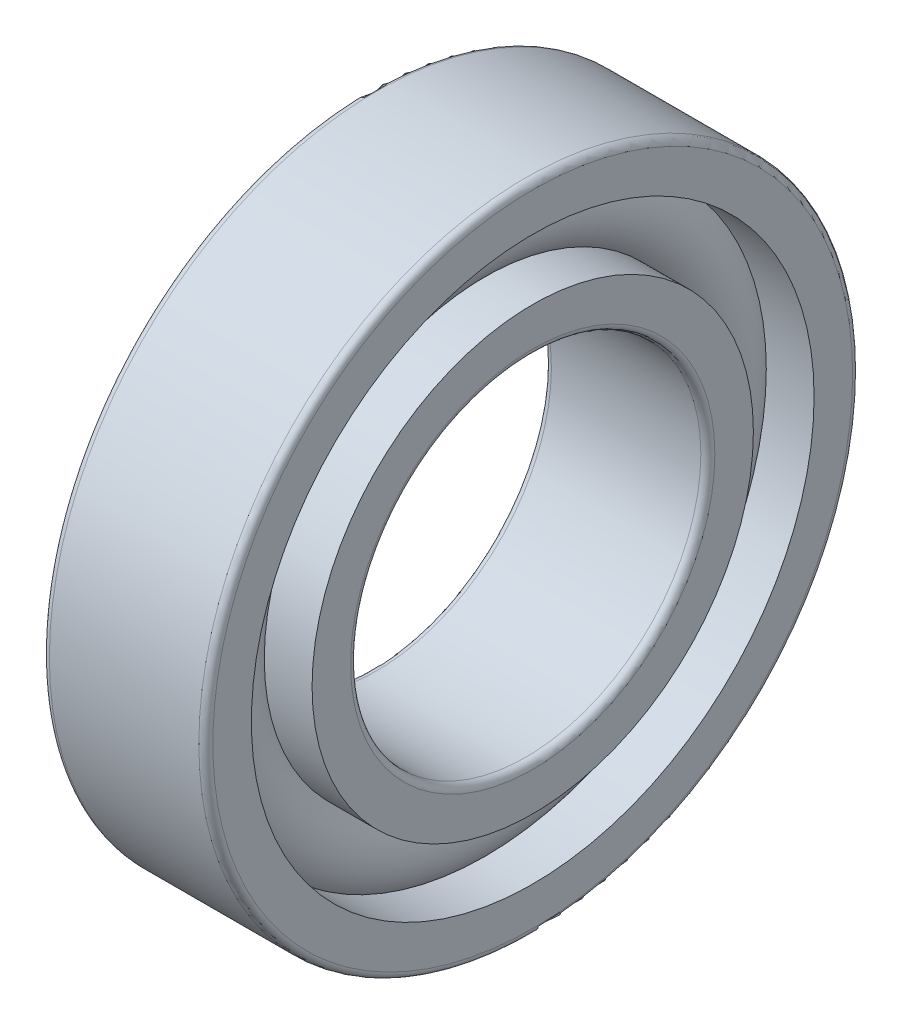
SolidWorks part; units mm, degrees
ref_plane "Plane1" through (0, 0, 0) normal (0, 0, 1) x (1, 0, 0)
ref_plane "Plane2" through (0, 0, 0) normal (0, 1, 0) x (1, 0, 0)
ref_plane "Plane3" through (0, 0, 0) normal (1, 0, 0) x (0, 0, -1)
sketch "Clipboard" plane through (0, 0, 0) normal (0, 0, 1) x (1, 0, 0)
  line L0 (-10, 0) -> (10, 0) construction
  line L1 (0, 0) -> (22.3471, -0.7804)
  line L2 (0, 0) -> (10.7435, 0.3752)
  line L3 (0, 0) -> (22.3471, -0.7804)
  line L4 (0, 0) -> (-22.3573, -0.3902)
  dimension "BallCLRad" = 10.75
sketch "CagSpiSke" plane through (0, 0, 0) normal (0, 0, 1) x (1, 0, 0)
  line L0 (0.195, 10.425) -> (0.195, 11.075)
  line L1 (0.195, 11.075) -> (-0.195, 11.075)
  line L2 (-0.195, 11.075) -> (-0.195, 10.425)
  line L3 (-0.195, 10.425) -> (0.195, 10.425)
  line L4 (-20.6375, 0) -> (20.6375, 0) construction
  line L5 (0, 0) -> (0, 23.7692) construction
  dimension "OD" = 22.15
  dimension "ID" = 20.85
revolve "CageSpine" add sketch "CagSpiSke" angle 0.001 about L4 reverse direction yes
ref_axis "Axis1" through (-50, 0, 0) along (1, 0, 0)
sketch "CagBalSke" plane through (0, 0, 0) normal (0, 0, 1) x (1, 0, 0)
  line L0 (-2.145, 10.75) -> (2.145, 10.75)
  line L1 (-1.905, 10.75) -> (1.905, 10.75) construction
  line L2 (-10, 0) -> (10, 0) construction
  line L3 (0, 0) -> (0, 24) construction
  arc A0 (2.145, 10.75) -> (-2.145, 10.75) centre (0, 10.75) cw
  dimension "BallCLRad" = 10.75
revolve "CageBall" [suppressed] add sketch "CagBalSke" angle 360 about L1 reverse direction yes
pattern_circular "CageBalls" [suppressed] count 2 every 180 about axis through (-50, 0, 0) along (1, 0, 0)
sketch "CagTrmODSke" plane through (0, 0, 0) normal (0, 0, 1) x (1, 0, 0)
  line L0 (2.146, 11.075) -> (2.146, 12.896)
  line L1 (2.146, 12.896) -> (-2.146, 12.896)
  line L2 (-2.146, 12.896) -> (-2.146, 11.075)
  line L3 (-2.146, 11.075) -> (2.146, 11.075)
  line L4 (-20.6375, 0) -> (20.6375, 0) construction
  line L5 (0, 0) -> (0, 25) construction
  dimension "Width" = 4.292
  dimension "ID" = 22.15
  dimension "OD" = 25.792
revolve "CageTrimOD" [suppressed] cut sketch "CagTrmODSke" angle 360 about L4 reverse direction yes
sketch "CagTrmIDSke" plane through (0, 0, 0) normal (0, 0, 1) x (1, 0, 0)
  line L0 (2.146, 8.606) -> (2.146, 10.425)
  line L1 (2.146, 10.425) -> (-2.146, 10.425)
  line L2 (-2.146, 10.425) -> (-2.146, 8.606)
  line L3 (-2.146, 8.606) -> (2.146, 8.606)
  line L4 (-20.6375, 0) -> (20.6375, 0) construction
  line L5 (0, 0) -> (0, 25) construction
  dimension "Width" = 4.292
  dimension "ID" = 17.212
  dimension "OD" = 20.85
revolve "CageTrimID" [suppressed] cut sketch "CagTrmIDSke" angle 360 about L4 reverse direction yes
sketch "BalSimSke" plane through (0, 0, 0) normal (0, 0, 1) x (1, 0, 0)
  line L0 (-10, 0) -> (10, 0) construction
  line L1 (-10, 10.75) -> (10, 10.75) construction
  line L2 (0, 0) -> (0, 23) construction
  circle A0 centre (0, 10.75) radius 1.95
  dimension "BallCLRad" = 10.75
  dimension "Ball_diameter" = 3.9
revolve "BallsSimplified" add sketch "BalSimSke" angle 360 about L0
sketch "BalDetSke" plane through (0, 0, 0) normal (0, 0, 1) x (1, 0, 0)
  line L0 (-1.95, 10.75) -> (1.95, 10.75)
  line L1 (-1.905, 10.75) -> (1.905, 10.75) construction
  line L2 (0, 0) -> (0, 25) construction
  arc A0 (1.95, 10.75) -> (-1.95, 10.75) centre (0, 10.75) cw
  dimension "BallCLRad" = 10.75
  dimension "Ball_diameter" = 3.9
revolve "BallDetailed" [suppressed] add sketch "BalDetSke" angle 360 about L1 reverse direction yes
sketch "InnRacSke" plane through (0, 0, 0) normal (0, 0, 1) x (1, 0, 0)
  line L0 (-1.4197, 9.45) -> (-3.5, 9.45)
  line L1 (-3.5, 9.45) -> (-3.5, 7.8)
  line L2 (-3.2, 7.5) -> (3.2, 7.5)
  line L3 (3.5, 7.8) -> (3.5, 9.45)
  line L4 (3.5, 9.45) -> (1.4197, 9.45)
  line L5 (-20.6375, 0) -> (20.6375, 0) construction
  line L6 (0, 0) -> (0, 30) construction
  arc A0 (-3.5, 7.8) -> (-3.2, 7.5) centre (-3.2, 7.8) ccw
  arc A1 (3.2, 7.5) -> (3.5, 7.8) centre (3.2, 7.8) ccw
  arc A2 (1.4197, 9.45) -> (-1.4197, 9.45) centre (0, 10.75) cw
  dimension "BallCLRad" = 10.75
  dimension "Fillet_radius" = 0.3
  dimension "Ball_diameter" = 3.85
  dimension "ID" = 15
  dimension "OD" = 18.9
  dimension "Width" = 7
revolve "InnerRace" add sketch "InnRacSke" angle 360 about L5 reverse direction yes
sketch "OutRacSke" plane through (0, 0, 0) normal (0, 0, 1) x (1, 0, 0)
  line L0 (-1.4197, 12.05) -> (-3.5, 12.05)
  line L1 (-3.5, 12.05) -> (-3.5, 13.7)
  line L2 (-3.2, 14) -> (3.2, 14)
  line L3 (3.5, 13.7) -> (3.5, 12.05)
  line L4 (3.5, 12.05) -> (1.4197, 12.05)
  line L5 (-20.6375, 0) -> (20.6375, 0) construction
  line L6 (0, 0) -> (0, 30) construction
  arc A0 (-3.5, 13.7) -> (-3.2, 14) centre (-3.2, 13.7) cw
  arc A1 (3.2, 14) -> (3.5, 13.7) centre (3.2, 13.7) cw
  arc A2 (1.4197, 12.05) -> (-1.4197, 12.05) centre (0, 10.75) ccw
  dimension "BallCLRad" = 10.75
  dimension "Fillet_radius" = 0.3
  dimension "Ball_diameter" = 3.85
  dimension "Width" = 7
revolve "OuterRace" add sketch "OutRacSke" angle 360 about L5 reverse direction yes
pattern_circular "BallsDetailed" [suppressed] count 2 every 180 about axis through (-50, 0, 0) along (1, 0, 0)
equation "\"BallCLRad@Clipboard\" = ( \"OD@OutRacSke\" + \"ID@InnRacSke\" ) / 4"
equation "\"BallCLRad@BalSimSke\" = \"BallCLRad@Clipboard\""
equation "\"BallCLRad@BalDetSke\" = \"BallCLRad@Clipboard\""
equation "\"BallCLRad@InnRacSke\" = \"BallCLRad@Clipboard\""
equation "\"BallCLRad@OutRacSke\" = \"BallCLRad@Clipboard\""
equation "\"Ball_diameter@InnRacSke\" = \"Ball_diameter@BalDetSke\" - 0.05"
equation "\"Ball_diameter@OutRacSke\" = \"Ball_diameter@BalDetSke\" - 0.05"
equation "\"Ball_diameter@BalSimSke\" = \"Ball_diameter@BalDetSke\""
equation "\"Width@OutRacSke\" = \"Width@InnRacSke\""
equation "\"Fillet_radius@OutRacSke\" = \"Fillet_radius@InnRacSke\""
equation "\"Max_count@Clipboard\" = int( 3.14159265 / atn(( \"Ball_diameter@BalDetSke\" / 2) / sqr( \"BallCLRad@Clipboard\"  *  \"BallCLRad@Clipboard\" - ( \"Ball_diameter@BalDetSke\" / 2) *  ( \"Ball_diameter@BalDetSke\" / 2))))"
equation "\"Max_count@Clipboard\" = ((sgn( \"Max_count@Clipboard\" - \"Count@Clipboard\" )-1)*( \"Max_count@Clipboard\" - \"Count@Clipboard\" ))/-2+ \"Count@Clipboard\""
equation "\"Count@BallsDetailed\" = int( \"Show_count@Clipboard\" ) "
equation "\"Count@BallsDetailed\" = ((sgn( \"Count@BallsDetailed\" - \"Max_count@Clipboard\" )-1)*( \"Count@BallsDetailed\" - \"Max_count@Clipboard\" ))/-2+ \"Max_count@Clipboard\""
equation "\"Count@BallsDetailed\" = ((sgn( \"Count@BallsDetailed\" - \"Min_count@Clipboard\" )+1)*( \"Count@BallsDetailed\" - \"Min_count@Clipboard\"))/2 +\"Min_count@Clipboard\""
equation "\"Angle@BallsDetailed\" = 360.0 / \"Max_count@Clipboard\""
equation "\"BallCLRad@CagBalSke\" = \"BallCLRad@Clipboard\""
equation "\"Count@CageBalls\" = \"Count@BallsDetailed\""
equation "\"Angle@CageBalls\" = \"Angle@BallsDetailed\""
equation "\"Angle@CageSpine\" =  \"Angle@CageBalls\" * ( \"Count@CageBalls\" -1 + int( \"Count@CageBalls\" / \"Max_count@Clipboard\" ) )  + 0.001 -  int( \"Count@CageBalls\" / \"Max_count@Clipboard\" ) * 0.001"
equation "\"Angle@CageSpine\" =  \"Angle@CageSpine\" * int( \"Min_count@Clipboard\" / 2) + int(1 / \"Min_count@Clipboard\")  * 0.001"
equation "\"CageWallOD@CagBalSke\" =  \"Ball_diameter@BalDetSke\" * 1.1"
equation "\"Thickness@CagSpiSke\" =  \"Ball_diameter@BalDetSke\" * 0.1"
equation "\"OD@CagTrmODSke\" = \"BallCLRad@Clipboard\" * 2 + \"CageWallOD@CagBalSke\" + 0.002"
equation "\"ID@CagTrmODSke\" = \"BallCLRad@Clipboard\" * 2 + \"Ball_diameter@BalDetSke\" / 6"
equation "\"OD@CagTrmIDSke\" = \"BallCLRad@Clipboard\" * 2 - \"Ball_diameter@BalDetSke\" / 6"
equation "\"ID@CagTrmIDSke\" = \"BallCLRad@Clipboard\" * 2 - \"CageWallOD@CagBalSke\" + 0.002"
equation "\"OD@CagSpiSke\" = \"ID@CagTrmODSke\""
equation "\"ID@CagSpiSke\" = \"OD@CagTrmIDSke\""
equation "\"Width@CagTrmODSke\" = \"CageWallOD@CagBalSke\" + 0.002"
equation "\"Width@CagTrmIDSke\" = \"CageWallOD@CagBalSke\" + 0.002"
